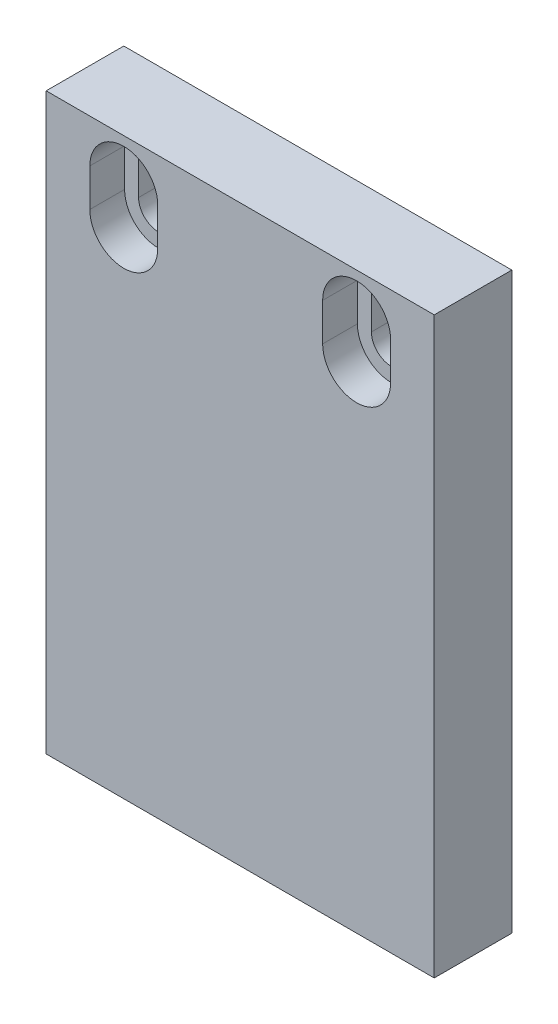
SolidWorks part; units mm, degrees
ref_plane "Front Plane" through (0, 0, 0) normal (0, 0, 1) x (1, 0, 0)
ref_plane "Top Plane" through (0, 0, 0) normal (0, 1, 0) x (1, 0, 0)
ref_plane "Right Plane" through (0, 0, 0) normal (1, 0, 0) x (0, 0, -1)
sketch "Sketch1" plane through (0, 0, 0) normal (0, 1, 0) x (1, 0, 0)
  line L1 (15.875, -3.175) -> (-15.875, -3.175)
  line L2 (15.875, -3.175) -> (15.875, 3.175)
  line L3 (15.875, 3.175) -> (-15.875, 3.175)
  line L4 (-15.875, -3.175) -> (-15.875, 3.175)
  line L5 (15.875, -3.175) -> (-15.875, 3.175) construction
  line L6 (15.875, 3.175) -> (-15.875, -3.175) construction
  point P0 (0, 0)
  dimension "D1" = 6.35
  dimension "D2" = 31.75
extrude "Boss-Extrude1" add sketch "Sketch1" along normal blind 46.99 contours L3 L4 L1 L2
hole_wizard "#4-40 Tapped Hole1" positions "Sketch2" profile "Sketch3" tap size "#4-40" standard "ANSI Inch"
sketch "Sketch2" plane through (0, 0, 0) normal (0, -1, 0) x (-1, 0, 0)
  line L0 (15.875, -3.175) -> (15.875, 3.175) construction
  line L1 (-15.875, -3.175) -> (-15.875, 3.175) construction
  point P0 (9.525, 0)
  point P2 (-9.525, 0)
  dimension "D1" = 6.35
  dimension "D2" = 6.35
sketch "Sketch3" plane through (-9.525, 0, 0) normal (1, 0, 0) x (0, 0, -1)
  line L0 (0, 0) -> (0, 8.2738)
  line L1 (0, 8.2738) -> (1.1303, 7.5946)
  line L2 (1.1303, 7.5946) -> (1.1303, 0)
  line L5 (1.1303, 0) -> (0, 0)
  line L10 (0, 8.2738) -> (-1.1303, 7.5946) construction
  line L11 (0, -6.35) -> (0, 107.95) construction
  dimension "Tap Drill Dia." = 2.2606
  dimension "Tap Drill Depth" = 7.5946
  dimension "Drill Angle" = 118
cosmetic thread "Hole Thread1" parameters "D1"=5.6896, "D2"=2.8448
cosmetic thread "Hole Thread2" parameters "D1"=5.6896, "D2"=2.8448
hole_wizard "CBORE SLOT for #4 Socket Head Cap Screw1" positions "Sketch4" profile "Sketch5" size "#4" standard "ANSI Inch" slot yes
sketch "Sketch4" plane through (0, 0, 3.175) normal (0, 0, 1) x (1, 0, 0)
  line L0 (9.525, 38.735) -> (9.525, 45.085) construction
  line L1 (15.875, 46.99) -> (-15.875, 46.99) construction
  line L2 (15.875, 46.99) -> (15.875, 0) construction
  line L3 (-15.875, 46.99) -> (-15.875, 0) construction
  point P0 (9.525, 41.91)
  point P4 (-9.525, 41.91)
  dimension "D1" = 6.35
  dimension "D2" = 6.35
  dimension "D3" = 5.08
  dimension "D4" = 6.35
  dimension "D5" = 5.08
sketch "Sketch5" plane through (9.525, 41.91, 3.175) normal (1, 0, 0) x (0, -1, 0)
  line L0 (0, 0) -> (0, 17.4906)
  line L1 (0, 17.4906) -> (1.6319, 16.51)
  line L2 (1.6319, 16.51) -> (1.6319, 2.8448)
  line L3 (1.6319, 2.8448) -> (2.7788, 2.8448)
  line L4 (2.7788, 2.8448) -> (2.7788, 0)
  line L5 (2.7788, 0) -> (0, 0)
  line L10 (0, 17.4906) -> (-1.632, 16.51) construction
  line L11 (0, -6.35) -> (0, 107.95) construction
  dimension "Hole Dia." = 3.2639
  dimension "Hole Depth" = 16.51
  dimension "C'Bore Dia." = 5.5575
  dimension "C'Bore Depth" = 2.8448
  dimension "Drill Angle" = 118
